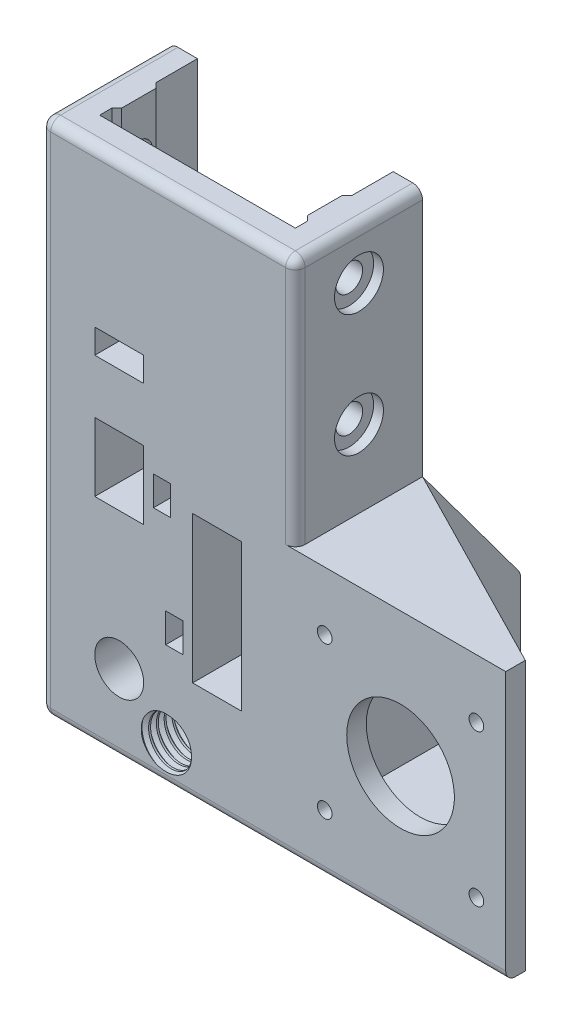
SolidWorks part; units mm, degrees
ref_plane "Front Plane" through (0, 0, 0) normal (0, 0, 1) x (1, 0, 0)
ref_plane "Top Plane" through (0, 0, 0) normal (0, 1, 0) x (1, 0, 0)
ref_plane "Right Plane" through (0, 0, 0) normal (1, 0, 0) x (0, 0, -1)
sketch "Sketch1" plane through (0, 0, 0) normal (1, 0, 0) x (0, 0, -1)
  line L0 (0, 106) -> (26, 106)
  line L1 (0, 0) -> (46, 0)
  line L2 (0, 106) -> (0, 0)
  line L3 (46, 0) -> (46, 55)
  line L4 (26, 106) -> (26, 55)
  line L5 (26, 55) -> (46, 55)
  line L6 (6, 106) -> (6, 58)
  line L7 (46, 6) -> (26, 6)
  line L8 (6, 58) -> (26, 58)
  line L10 (26, 55) -> (26, 6)
  circle A0 centre (13, 95.75) radius 2.75
  circle A1 centre (13, 95.75) radius 5
  circle A2 centre (13, 70.75) radius 2.75
  circle A3 centre (13, 70.75) radius 5
  circle A4 centre (36.25, 15.75) radius 2.75
  circle A5 centre (36.25, 15.75) radius 5
  point P9 (13, 106)
  point P15 (8.8717, 6)
  point P19 (26, 58)
  point P20 (35.1327, 30.1857)
  point P21 (26, 6)
  point P26 (35.8678, 13.2319)
  dimension "D6" = 2.75
  dimension "D7" = 5
  dimension "D1" = 46
  dimension "D2" = 26
  dimension "D3" = 106
  dimension "D4" = 55
  dimension "D5" = 10.25
  dimension "D8" = 25
  dimension "D9" = 6
  dimension "D10" = 6
  dimension "D11" = 58
  dimension "D12" = 15.75
  dimension "D13" = 9.75
extrude "Boss-Extrude1" add sketch "Sketch1" along normal mid plane 52 contours L10 L4 L8 L6 L0 L2 L1 L3 L7 | L5 L10 L7 L3 | A3 A2 | A1 A0 | L6 L8 L4 L0 A3 A1 | A5 A4 region at (0, 35.3382, -12.9374) region at (0, 81.7555, -16.5869) region at (0, 31.7851, -35.9782) region at (0, 95.75, -8.1414) region at (0, 70.75, -8.1414) region at (0, 15.75, -31.3914)
chamfer "Chamfer1" distance 27 distance2 20 1 edges at (0, 55, -46) first distance on face at (0, 27.5, -46)
extrude "Cut-Extrude1" cut sketch "Sketch1<3>" against normal mid plane 40 contours L5 L10 L7 L3 | L6 L8 L4 L0 A3 A1 | A3 A2 | A1 A0 | A5 A4 region at (0, 81.7555, -16.5869) region at (0, 31.7851, -35.9782) region at (0, 95.75, -8.1414) region at (0, 70.75, -8.1414) region at (0, 15.75, -31.3914)
sketch "Sketch1<3>" plane through (0, 0, 0) normal (1, 0, 0) x (0, 0, -1) same geometry as "Sketch1"
sketch "Sketch2" plane through (0, 0, -26) normal (0, 0, -1) x (-1, 0, 0)
  line L0 (20, 58) -> (-20, 58) construction
  line L1 (-20, 58) -> (-5, 58)
  line L2 (-20, 58) -> (-20, 46)
  line L3 (-20, 46) -> (-5, 46)
  line L4 (-5, 58) -> (-5, 46)
  line L5 (5, 58) -> (15, 58)
  line L6 (5, 58) -> (5, 44)
  line L7 (5, 44) -> (15, 44)
  line L8 (15, 58) -> (15, 44)
  dimension "D1" = 15
  dimension "D2" = 12
  dimension "D3" = 10
  dimension "D4" = 14
  dimension "D5" = 10
extrude "Cut-Extrude2" cut sketch "Sketch2" against normal up to surface (20 mm away) up to face at (0, 82, -6)
sketch "Sketch3" plane through (0, 0, 0) normal (0, 0, 1) x (1, 0, 0)
  line L0 (5, 51) -> (15, 51)
  line L1 (-15, 74) -> (-5, 74)
  line L2 (-15, 74) -> (-15, 44)
  line L3 (-15, 44) -> (-5, 44)
  line L4 (-5, 74) -> (-5, 44)
  line L5 (5, 51) -> (5, 21)
  line L6 (-5, 44) -> (-15, 44) construction
  line L7 (-15, 44) -> (-15, 58) construction
  line L8 (-15, 69) -> (-5, 69)
  line L9 (-15, 58) -> (-5, 58)
  line L10 (-20, 58) -> (-15, 58) construction
  line L11 (5, 21) -> (15, 21)
  line L12 (15, 51) -> (15, 21)
  line L13 (5, 46) -> (15, 46)
  line L14 (5, 35) -> (15, 35)
  line L15 (20, 46) -> (5, 46) construction
  line L16 (5, 46) -> (5, 58) construction
  line L17 (10, 21) -> (10, 35) construction
  line L18 (-10, 44) -> (-10, 58) construction
  line L19 (0.5, 48) -> (-3, 48)
  line L20 (3, 25) -> (-0.5, 25)
  line L21 (3, 25) -> (3, 31)
  line L22 (3, 31) -> (-0.5, 31)
  line L23 (-0.5, 25) -> (-0.5, 31)
  line L24 (3, 25) -> (-0.5, 31) construction
  line L25 (3, 31) -> (-0.5, 25) construction
  line L26 (0.5, 48) -> (0.5, 54)
  line L27 (0.5, 54) -> (-3, 54)
  line L28 (-3, 48) -> (-3, 54)
  line L29 (0.5, 48) -> (-3, 54) construction
  line L30 (0.5, 54) -> (-3, 48) construction
  circle A0 centre (-10, 16) radius 5
  circle A1 centre (-10, 16) radius 2.75
  point P23 (-10, 44)
  point P34 (1.25, 28)
  point P39 (0, 0)
  point P40 (10, 28)
  point P41 (-2.506, 28)
  point P42 (-1.25, 51)
  point P47 (-10, 51)
  dimension "D9" = 5
  dimension "D10" = 2.75
  dimension "D1" = 11
  dimension "D2" = 10
  dimension "D3" = 10
  dimension "D4" = 5
  dimension "D5" = 5
  dimension "D6" = 11
  dimension "D7" = 14
  dimension "D8" = 28
  dimension "D11" = 3.5
  dimension "D12" = 6
  dimension "D13" = 2
  dimension "D14" = 3.5
  dimension "D15" = 6
  dimension "D16" = 2
extrude "Cut-Extrude3" cut sketch "Sketch3" against normal through all contours A1 | L5 L13 L12 L0 | L14 L5 L11 L12 | L9 L2 L3 L4 | L2 L8 L4 L1 region at (10, 48.5, 0) region at (10, 28, 0) region at (-10, 71.5, 0) region at (-10, 51, 0) region at (-10, 16, 0)
extrude "Cut-Extrude4" cut sketch "Sketch3<3>" against normal blind 22 contours A0 A1 | L23 L20 L21 L22 | L28 L19 L26 L27 region at (-1.25, 51, 0) region at (1.25, 28, 0) region at (-14.8586, 16, 0)
sketch "Sketch3<3>" plane through (0, 0, 0) normal (0, 0, 1) x (1, 0, 0) same geometry as "Sketch3"
extrude "Cut-Extrude5" cut sketch "Sketch3<4>" against normal blind 11 contours L5 L14 L12 L13 region at (10, 40.5, 0)
sketch "Sketch3<4>" plane through (0, 0, 0) normal (0, 0, 1) x (1, 0, 0) same geometry as "Sketch3"
sketch "Sketch4" plane through (0, 0, 0) normal (1, 0, 0) x (0, 0, -1)
  line L0 (26, 21) -> (26, 35) construction
  line L2 (26, 44) -> (26, 58) construction
  line L3 (0, 106) -> (0, 0) construction
  circle A0 centre (14, 28) radius 1.5
  circle A1 centre (14, 28) radius 3
  circle A2 centre (14, 51) radius 1.5
  circle A3 centre (14, 51) radius 3
  point P3 (10.9426, 24.6286)
  point P6 (0, 0)
  point P7 (26, 28)
  point P8 (0, 0)
  point P15 (12.7722, 46.8378)
  point P16 (0, 0)
  point P17 (0, 0)
  point P20 (26, 51)
  point P21 (0, 0)
  point P22 (19.6179, 28)
  dimension "D1" = 6
  dimension "D2" = 3
  dimension "D3" = 14
extrude "Cut-Extrude6" cut sketch "Sketch4" against normal up to surface (15 mm away) and the other way through all contours A0 region at (0, 28, -14) up to face at (-15, 52.4, -11.6)
extrude "Cut-Extrude7" cut sketch "Sketch4<3>" against normal through all and the other way up to surface (15 mm away) contours A2 region at (0, 51, -14) other way up to face at (15, 26.5, -14)
sketch "Sketch4<3>" plane through (0, 0, 0) normal (1, 0, 0) x (0, 0, -1) same geometry as "Sketch4"
extrude "Cut-Extrude8" cut sketch "Sketch4<4>" against normal blind 8 from surface contours A1 A0 region at (0, 28, -11.0849) starting at face at (26, 28, -15.5)
sketch "Sketch4<4>" plane through (0, 0, 0) normal (1, 0, 0) x (0, 0, -1) same geometry as "Sketch4"
extrude "Cut-Extrude9" cut sketch "Sketch4<5>" along normal blind 8 from surface contours A3 A2 region at (0, 51, -11.0849) starting at face at (-26, 51, -15.5)
sketch "Sketch4<5>" plane through (0, 0, 0) normal (1, 0, 0) x (0, 0, -1) same geometry as "Sketch4"
extrude "Cut-Extrude10" cut sketch "Sketch1<4>" against normal blind 2 from surface contours A1 A0 | A3 A2 | A5 A4 region at (0, 95.75, -8.1414) region at (0, 70.75, -8.1414) region at (0, 15.75, -31.3914) starting at face at (26, 28, -17)
sketch "Sketch1<4>" plane through (0, 0, 0) normal (1, 0, 0) x (0, 0, -1) same geometry as "Sketch1"
extrude "Cut-Extrude11" cut sketch "Sketch1<5>" along normal blind 2 from surface contours A5 A4 | A3 A2 | A1 A0 region at (0, 95.75, -8.1414) region at (0, 70.75, -8.1414) region at (0, 15.75, -31.3914) starting at face at (-26, 70.75, -15.75)
sketch "Sketch1<5>" plane through (0, 0, 0) normal (1, 0, 0) x (0, 0, -1) same geometry as "Sketch1"
sketch "Sketch5" plane through (0, 0, -46) normal (0, 0, -1) x (-1, 0, 0)
  line L0 (0, 0) -> (0, 106) construction
  line L1 (20, 106) -> (-20, 106) construction
  line L2 (20, 6) -> (-20, 6) construction
  line L3 (-14.25, 6) -> (-5.25, 6)
  line L4 (-14.25, 6) -> (-14.25, 7)
  line L5 (-14.25, 7) -> (-5.25, 7)
  line L6 (-5.25, 6) -> (-5.25, 7)
  line L7 (5.25, 6) -> (5.25, 7)
  line L8 (14.25, 7) -> (5.25, 7)
  line L9 (14.25, 6) -> (14.25, 7)
  line L10 (14.25, 6) -> (5.25, 6)
  line L11 (-20, 46) -> (-20, 6) construction
  line L12 (-20, 20.25) -> (-19, 20.25)
  line L13 (-20, 20.25) -> (-20, 11.25)
  line L14 (-20, 11.25) -> (-19, 11.25)
  line L15 (-19, 20.25) -> (-19, 11.25)
  line L16 (19, 20.25) -> (19, 11.25)
  line L17 (20, 11.25) -> (19, 11.25)
  line L18 (20, 20.25) -> (20, 11.25)
  line L19 (20, 20.25) -> (19, 20.25)
  line L20 (-26, 20.75) -> (-26, 10.75) construction
  line L21 (-26, 20.75) -> (-26, 10.75) construction
  point P29 (-26, 15.75)
  point P30 (-20, 15.75)
  dimension "D1" = 9
  dimension "D2" = 1
  dimension "D3" = 10.5
  dimension "D4" = 9
  dimension "D5" = 1
sketch "Sketch6" plane through (0, 6, 0) normal (0, 1, 0) x (1, 0, 0)
  line L0 (19, 17.5) -> (19, 8.5)
  line L1 (-24, 15.75) -> (-24, 10.25) construction
  line L2 (-14.25, 46) -> (-5.25, 46) construction
  line L3 (-20, 6) -> (-20, 26) construction
  line L4 (-20, 17.5) -> (-19, 17.5)
  line L5 (-20, 17.5) -> (-20, 8.5)
  line L6 (-20, 8.5) -> (-19, 8.5)
  line L7 (-19, 17.5) -> (-19, 8.5)
  line L8 (0, 46) -> (0, 0) construction
  line L9 (-20, 46) -> (20, 46) construction
  line L10 (-24, 15.75) -> (-24, 10.25) construction
  line L11 (20, 8.5) -> (19, 8.5)
  line L12 (20, 17.5) -> (20, 8.5)
  line L13 (20, 17.5) -> (19, 17.5)
  circle A0 centre (-9.75, 36.25) radius 2.75
  circle A1 centre (-9.75, 36.25) radius 5
  circle A2 centre (9.75, 36.25) radius 5
  circle A3 centre (9.75, 36.25) radius 2.75
  point P6 (-9.75, 46)
  point P17 (-19, 31.7229)
  point P18 (-20, 13)
  point P21 (-24, 13)
  dimension "D1" = 5.5
  dimension "D2" = 10
  dimension "D3" = 9.75
  dimension "D4" = 9
  dimension "D5" = 1
extrude "Boss-Extrude2" add sketch "Sketch4<6>" against normal blind 0.5 from surface contours A3 A2 region at (0, 51, -11.0849) starting at face at (-5, 52.5, -14)
sketch "Sketch4<6>" plane through (0, 0, 0) normal (1, 0, 0) x (0, 0, -1) same geometry as "Sketch4"
extrude "Boss-Extrude3" add sketch "Sketch4<7>" along normal blind 0.5 from surface contours A3 A2 region at (0, 51, -11.0849) starting at face at (-15, 49.5, -14)
sketch "Sketch4<7>" plane through (0, 0, 0) normal (1, 0, 0) x (0, 0, -1) same geometry as "Sketch4"
extrude "Boss-Extrude4" add sketch "Sketch4<8>" along normal blind 0.5 from surface contours A1 A0 region at (0, 28, -11.0849) starting at face at (5, 49.5, -14)
sketch "Sketch4<8>" plane through (0, 0, 0) normal (1, 0, 0) x (0, 0, -1) same geometry as "Sketch4"
extrude "Boss-Extrude5" add sketch "Sketch4<9>" against normal blind 0.5 from surface contours A1 A0 region at (0, 28, -11.0849) starting at face at (15, 26.5, -14)
sketch "Sketch4<9>" plane through (0, 0, 0) normal (1, 0, 0) x (0, 0, -1) same geometry as "Sketch4"
extrude "Boss-Extrude6" add sketch "Sketch5" against normal up to surface (20 mm away) up to face at (-10, 18.75, -26)
extrude "Boss-Extrude7" add sketch "Sketch6" against normal up to body from surface separate body contours L12 L13 L0 L11 | L7 L4 L5 L6 region at (19.5, 6, -13) region at (-19.5, 6, -13) starting at face at (0, 106, -14.5)
extrude "Cut-Extrude12" cut sketch "Sketch1<6>" against normal through all both and the other way through all contours A0 | A2 | A4 region at (0, 95.75, -13) region at (0, 70.75, -13) region at (0, 15.75, -36.25)
sketch "Sketch1<6>" plane through (0, 0, 0) normal (1, 0, 0) x (0, 0, -1) same geometry as "Sketch1"
extrude "Cut-Extrude13" cut sketch "Sketch6<3>" against normal through all both and the other way through all contours A0 | A3 region at (-9.75, 6, -36.25) region at (9.75, 6, -36.25)
sketch "Sketch6<3>" plane through (0, 6, 0) normal (0, 1, 0) x (1, 0, 0) same geometry as "Sketch6"
extrude "Cut-Extrude14" cut sketch "Sketch6<4>" along normal blind 2 from surface contours A2 A3 | A1 A0 region at (-14.6086, 6, -36.25) region at (4.8914, 6, -36.25) starting at face at (0, 0, -23)
sketch "Sketch6<4>" plane through (0, 6, 0) normal (0, 1, 0) x (1, 0, 0) same geometry as "Sketch6"
chamfer "Chamfer2" distance 1 12 edges at (-19, 11.25, -36) (-19, 20.25, -36) (-5.25, 7, -36) (-14.25, 7, -36) (5.25, 7, -36) (14.25, 7, -36) (19, 11.25, -36) (19, 20.25, -36) (19, 76, -8.5) (19, 76, -17.5) (-19, 82, -8.5) (-19, 82, -17.5)
chamfer "Chamfer3" distance 0.5 angle 45 4 edges at (5.5, 25, -14) (14.5, 25, -14) (-5.5, 54, -14) (-14.5, 48, -14)
sketch "Sketch7" plane through (0, 0, 0) normal (0, 1, 0) x (1, 0, 0)
  line L0 (26, 0) -> (69, 0)
  line L2 (26, 46) -> (26, 0)
  line L3 (69, 4) -> (69, 0)
  line L4 (26, 4) -> (69, 4)
  line L5 (69, 4) -> (26, 46)
  line L6 (69, 4) -> (26, 26)
  dimension "D1" = 43
  dimension "D2" = 4
extrude "Boss-Extrude8" add sketch "Sketch7" along normal up to surface (6 mm away) contours L4 L2 L0 L3 | L4 L6 L2 | L6 L5 L2 region at (47.5, 0, -2) region at (40.3333, 0, -11.3333) region at (40.3333, 0, -25.3333) up to face at (17.125, 6, -36)
extrude "Boss-Extrude9" add sketch "Sketch7<3>" along normal blind 43 from surface contours L4 L2 L0 L3 region at (47.5, 0, -2) starting at face at (47.5, 6, -12.5)
sketch "Sketch7<3>" plane through (0, 0, 0) normal (0, 1, 0) x (1, 0, 0) same geometry as "Sketch7"
extrude "Boss-Extrude10" add sketch "Sketch7<4>" along normal blind 6 from surface contours L4 L6 L2 | L4 L2 L0 L3 region at (47.5, 0, -2) region at (40.3333, 0, -11.3333) starting at face at (47.5, 49, -2)
sketch "Sketch7<4>" plane through (0, 0, 0) normal (0, 1, 0) x (1, 0, 0) same geometry as "Sketch7"
sketch "Sketch8" plane through (0, 0, -4) normal (0, 0, -1) x (-1, 0, 0)
  line L0 (-69, 27.5) -> (-26, 27.5) construction
  line L1 (-69, 49) -> (-69, 6) construction
  line L2 (-26, 49) -> (-26, 6) construction
  line L3 (-47.5, 49) -> (-47.5, 6) construction
  line L4 (-69, 49) -> (-26, 49) construction
  line L5 (-69, 6) -> (-26, 6) construction
  circle A0 centre (-47.5, 27.5) radius 11
  circle A1 centre (-63, 43) radius 1.5
  circle A2 centre (-32, 43) radius 1.5
  circle A3 centre (-32, 12) radius 1.5
  circle A4 centre (-63, 12) radius 1.5
  dimension "D1" = 22
  dimension "D2" = 1.5
  dimension "D3" = 31
  dimension "D4" = 31
extrude "Cut-Extrude15" cut sketch "Sketch8" against normal through all
sketch "Sketch9" plane through (0, 0, 0) normal (0, 0, 1) x (1, 0, 0)
  line L0 (0, 0) -> (0, 106) construction
  line L1 (26, 106) -> (-26, 106) construction
  circle A0 centre (0, 8) radius 4.7625
  dimension "D1" = 9.525
  dimension "D2" = 8
extrude "Cut-Extrude16" cut sketch "Sketch9" against normal blind 9
sketch "Sketch15" plane through (0, 0, -26) normal (0, 0, -1) x (-1, 0, 0)
  line L0 (0, 0) -> (0, 106) construction
  line L1 (-26, 0) -> (26, 0) construction
  line L2 (20, 106) -> (-20, 106) construction
  line L3 (-5, 21) -> (-5, 6) construction
  line L4 (5.25, 6) -> (-5.25, 6) construction
  circle A0 centre (0, 13.5) radius 4.7625
  point P8 (0, 0)
  point P14 (0, 30.3519)
  point P15 (-5, 13.5)
  dimension "D1" = 9.525
sketch "Sketch16" plane through (0, 0, 0) normal (1, 0, 0) x (0, 0, -1)
  line L0 (26, 8.7375) -> (26, 18.2625) construction
  line L1 (26, 8.7375) -> (26, 18.2625) construction
  line L2 (9, 12.7625) -> (9, 3.2375) construction
  line L3 (9, 12.7625) -> (9, 3.2375) construction
  line L4 (9.5484, 8) -> (8.4433, 8) construction
  line L5 (26.4266, 13.5) -> (25.3209, 13.5) construction
  line L6 (24.198, 13.5) -> (20.0639, 13.5) construction
  line L7 (14.5728, 8) -> (10.7825, 8) construction
  spline S0 degree 3 poles (9, 8) (10.5, 8) (10.2757, 8.0045) (15.7718, 7.9699) (18.7522, 13.52) (24.5106, 13.4979) (24.5, 13.5) (26, 13.5) knots 0 0 0 0 0.129298 0.21867 0.81872 0.904353 1 1 1 1
  point P6 (0, 0)
  point P17 (10.9745, 8.3185)
  point P18 (0, 0)
  point P19 (0, 0)
  point P20 (24, 13.5)
  dimension "D3" = 12
  dimension "D4" = 12
  dimension "D5" = 5
  dimension "D6" = 5
  dimension "D1" = 2
  dimension "D2" = 2
sweep "Cut-Sweep1" cut profiles "Sketch15" path "Sketch16"
thread "Thread1" pitch 1.5875 method cut trim with start face yes trim with end face yes profile "Thread Profile1" start angle 0, offset 2, length 0, pitch 1.5875, diameter 9.525
ref_plane "Plane1" through (-4.7625, 8, 2) normal (0, -1, 0) x (-1, 0, 0)
sketch "Thread Profile1" plane through (-4.7625, 8, 2) normal (0, -1, 0) x (-1, 0, 0)
  line L0 (0, 0) -> (0, 1.5875) construction
  line L1 (0, 0) -> (0.8593, 0.4961)
  line L2 (0.8593, 0.4961) -> (0.8593, 0.6945)
  line L3 (0.8593, 0.6945) -> (0, 1.1906)
  line L4 (0.8593, 0.5953) -> (0, 0.5953) construction
  line L11 (0, 0) -> (0, 1.1906)
  point P2 (0, 0)
  dimension "Pitch" = 1.5875
  dimension "Profile_Angle" = 60
  dimension "Profile_Land" = 0.1984
  dimension "Profile_Height" = 0.8593
fillet "Fillet1" radius 2 10 edges at (26, 106, -13) (-26, 106, -13) (0, 106, 0) (-26, 53, 0) (-23, 28, -46) (23, 28, -46) (-26, 0, -23) (0, 0, -46) (21.5, 0, 0) (26, 80.5, 0)
